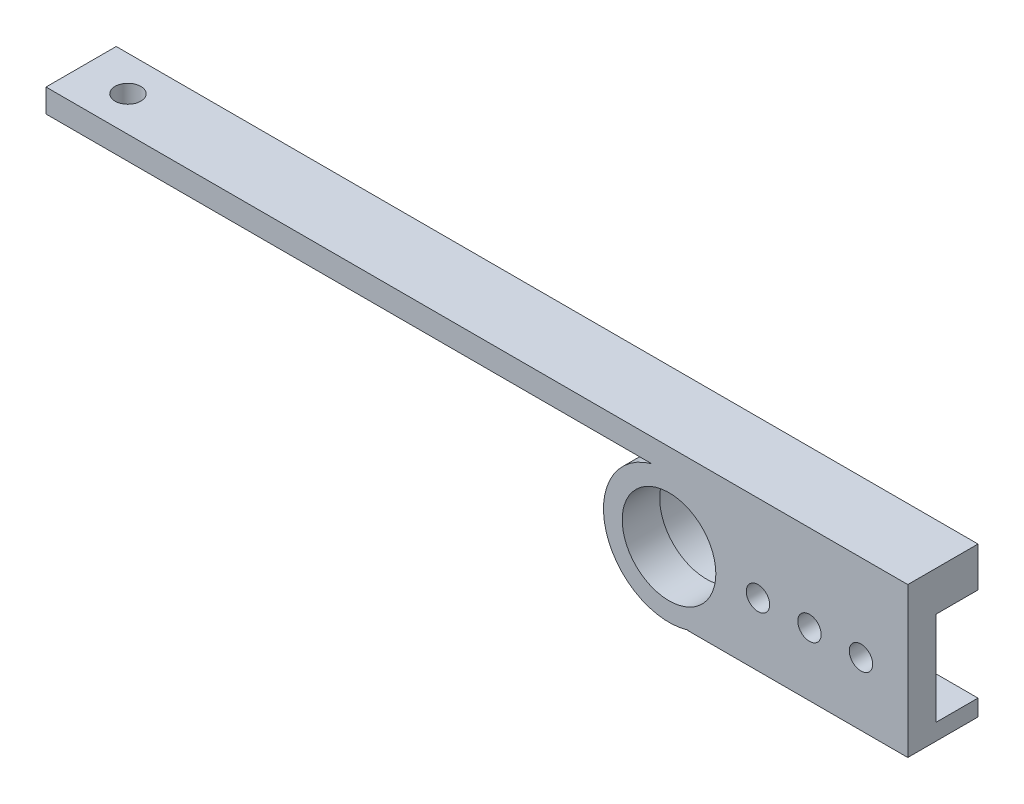
SolidWorks part; units mm, degrees
ref_plane "前视基准面" through (0, 0, 0) normal (0, 0, 1) x (1, 0, 0)
ref_plane "上视基准面" through (0, 0, 0) normal (0, 1, 0) x (1, 0, 0)
ref_plane "右视基准面" through (0, 0, 0) normal (1, 0, 0) x (0, 0, -1)
sketch "草图1" plane through (0, 0, 0) normal (0, 0, 1) x (1, 0, 0)
  line L1 (20, -10) -> (-20, -10)
  line L2 (20, -10) -> (20, 10)
  line L3 (20, 10) -> (-20, 10)
  line L4 (-20, -10) -> (-20, 10)
  line L5 (20, -10) -> (-20, 10) construction
  line L6 (20, 10) -> (-20, -10) construction
  point P0 (0, 0)
  dimension "D1" = 40
  dimension "D2" = 20
extrude "凸台-拉伸1" add sketch "草图1" along normal blind 6
sketch "草图2" plane through (0, 0, 6) normal (0, 0, 1) x (1, 0, 0)
  line L0 (20, -10) -> (20, 10) construction
  circle A0 centre (10, 0) radius 2.5
  circle A1 centre (-1, 0) radius 2.5
  circle A2 centre (-12, 0) radius 2.5
  dimension "D1" = 10
  dimension "D2" = 5
  dimension "D3" = 3
extrude "切除-拉伸1" cut sketch "草图2" against normal through all
sketch "草图3" plane through (0, 0, 6) normal (0, 0, 1) x (1, 0, 0)
  line L0 (20, 13.5) -> (20, 10)
  line L1 (20, -13.5) -> (-26.894, -13.5)
  line L3 (20, 13.5) -> (-26.894, 13.5)
  line L4 (-20, 10) -> (-20, -10)
  line L5 (-20, -10) -> (20, -10)
  line L6 (20, -10) -> (20, 10)
  line L7 (20, 10) -> (-20, 10)
  line L8 (-20, 10) -> (-20, -10)
  line L9 (-20, -10) -> (20, -10)
  line L10 (20, -10) -> (20, 10)
  line L11 (20, 10) -> (-20, 10)
  line L12 (-26.894, -13.5) -> (-26.894, 13.5)
  line L13 (20, -10.0394) -> (-26.894, 13.5) construction
  line L14 (20, 10.0394) -> (-26.894, -13.5) construction
  line L15 (20, -10) -> (20, -13.5)
  circle A0 centre (-31, 0) radius 11
  circle A1 centre (-31, 0) radius 14
  point P2 (0, 0)
  line M10 (-20, 10) -> (-20, -10)
  line M11 (-20, -10) -> (20, -10)
  line M13 (20, 10) -> (-20, 10)
  dimension "D3" = 22
  dimension "D4" = 28
  dimension "D2" = 3.5
  dimension "D1" = 0
extrude "凸台-拉伸2" add sketch "草图3" against normal blind 15 contours L3 A1 L1 L12 A0 | A1 L1 L15 M11 M10 | L1 A1 L8 A0 L12 | L8 A1 L3 L12 A0 | L8 A1 | A1 L0 L3 M10 M13 region at (-1.9449, 11.7771, 6) region at (-1.9449, -11.7771, 6) region at (-23.0173, 9.0328, 6) region at (-27.2274, 11.7946, 6) region at (-18.7882, 0, 6) region at (-23.0173, -9.0328, 6)
sketch "草图5" plane through (0, 0, 6) normal (0, 0, 1) x (1, 0, 0)
  circle A0 centre (-31, 0) radius 10
  circle A1 centre (-31, 0) radius 11 construction
  circle A2 centre (-31, 0) radius 11
  dimension "D1" = 20
extrude "凸台-拉伸3" add sketch "草图5" against normal blind 8
sketch "草图6" plane through (0, 0, 6) normal (0, 0, 1) x (1, 0, 0)
  circle A0 centre (-31, 0) radius 8.5
  circle A1 centre (-31, 0) radius 10 construction
  circle A2 centre (-31, 0) radius 10
  dimension "D1" = 17
sketch "草图7" plane through (0, 13.5, 0) normal (0, 1, 0) x (1, 0, 0)
  circle A0 centre (-16.8213, 3.0525) radius 3.3366
sketch "草图8" plane through (20, 0, 0) normal (1, 0, 0) x (0, 0, -1)
  line L1 (-6, 13.5) -> (9, 13.5)
  line L2 (-6, 13.5) -> (-6, 18.5)
  line L3 (-6, 18.5) -> (9, 18.5)
  line L4 (9, 13.5) -> (9, 18.5)
  dimension "D1" = 5
extrude "凸台-拉伸4" add sketch "草图8" against normal blind 200
sketch "草图9" plane through (0, 0, 6) normal (0, 0, 1) x (1, 0, 0)
  line L1 (-29.5663, 15.6648) -> (-25.1627, 15.6648)
  line L2 (-29.5663, 15.6648) -> (-29.5663, 11.9284)
  line L3 (-29.5663, 11.9284) -> (-25.1627, 11.9284)
  line L4 (-25.1627, 15.6648) -> (-25.1627, 11.9284)
extrude "凸台-拉伸5" add sketch "草图9" against normal through all
sketch "草图11" plane through (0, 18.5, 0) normal (0, 1, 0) x (1, 0, 0)
  line L0 (-118.4338, -6) -> (-118.4338, 9)
  line L1 (-180, -6) -> (20, -6) construction
  line L2 (-118.4338, 246.7017) -> (-118.4338, -123.2983) construction
  line L3 (-180, 9) -> (20, 9) construction
sketch "草图13" plane through (0, 18.5, 0) normal (0, 1, 0) x (1, 0, 0)
  line L1 (-118.4338, -6) -> (-183.1111, -6)
  line L2 (-118.4338, -6) -> (-118.4338, 12.5245)
  line L3 (-118.4338, 12.5245) -> (-183.1111, 12.5245)
  line L4 (-183.1111, -6) -> (-183.1111, 12.5245)
extrude "切除-拉伸2" cut sketch "草图13" against normal through all
sketch "草图14" plane through (0, 18.5, 0) normal (0, 1, 0) x (1, 0, 0)
  line L0 (-164.0842, 11.0465) -> (-164.0842, -39.4434)
  line L1 (-164.0842, 248.4982) -> (-164.0842, -121.5018) construction
sketch "草图15" plane through (0, 18.5, 0) normal (0, 1, 0) x (1, 0, 0)
  line L0 (-164.0842, 11.0465) -> (-164.0842, -39.4434) construction
  line L1 (-118.4338, -6) -> (-164.0842, -6)
  line L2 (-118.4338, -6) -> (-118.4338, 9)
  line L3 (-118.4338, 9) -> (-164.0842, 9)
  line L4 (-164.0842, -6) -> (-164.0842, 9)
extrude "凸台-拉伸6" add sketch "草图15" against normal blind 5
sketch "草图16" plane through (0, 18.5, 0) normal (0, 1, 0) x (1, 0, 0)
  line L0 (-164.0842, 1.5) -> (-154.0842, 1.5)
  line L1 (-164.0842, 11.0465) -> (-164.0842, -39.4434) construction
  circle A0 centre (-154.0842, 1.5) radius 2.75
  dimension "D2" = 5.5
  dimension "D1" = 10
extrude "切除-拉伸3" cut sketch "草图16" against normal blind 10 contours A0
